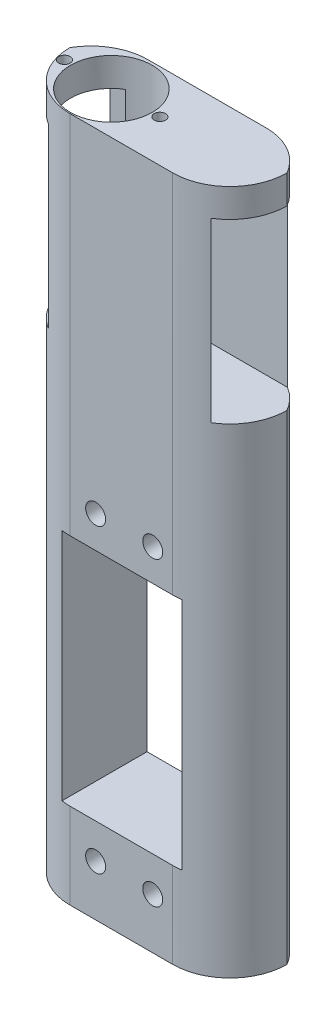
SolidWorks part; units mm, degrees
ref_plane "Front Plane" through (0, 0, 0) normal (0, 0, 1) x (1, 0, 0)
ref_plane "Top Plane" through (0, 0, 0) normal (0, 1, 0) x (1, 0, 0)
ref_plane "Right Plane" through (0, 0, 0) normal (1, 0, 0) x (0, 0, -1)
sketch "Sketch1" plane through (0, 0, 0) normal (0, 0, 1) x (1, 0, 0)
  line L1 (-20.7438, 48.8926) -> (17.2562, 48.8926)
  line L2 (-20.7438, 48.8926) -> (-20.7438, -71.1074)
  line L3 (-20.7438, -71.1074) -> (17.2562, -71.1074)
  line L4 (17.2562, 48.8926) -> (17.2562, -71.1074)
  dimension "D1" = 120
  dimension "D2" = 38
extrude "Boss-Extrude1" add sketch "Sketch1" along normal blind 15
sketch "Sketch2" plane through (0, 0, 15) normal (0, 0, 1) x (1, 0, 0)
  line L0 (-20.7438, -71.1074) -> (17.2562, -71.1074) construction
  line L1 (-12.2438, -15.1074) -> (8.7562, -15.1074)
  line L2 (-12.2438, -15.1074) -> (-12.2438, -56.1074)
  line L3 (-12.2438, -56.1074) -> (8.7562, -56.1074)
  line L4 (8.7562, -15.1074) -> (8.7562, -56.1074)
  line L5 (-20.7438, 48.8926) -> (-20.7438, -71.1074) construction
  dimension "D1" = 41
  dimension "D2" = 21
  dimension "D3" = 15
  dimension "D4" = 8.5
extrude "Cut-Extrude2" cut sketch "Sketch2" against normal blind 15 contours L2 L1 L4 L3
sketch "Sketch3" plane through (0, 0, 15) normal (0, 0, 1) x (1, 0, 0)
  circle A0 centre (-6.2438, -9.5176) radius 1.75
  circle A1 centre (3.7562, -9.5176) radius 1.75
  circle A3 centre (-6.2438, -62.2156) radius 1.75
  circle A4 centre (3.7562, -62.2156) radius 1.75
  dimension "D1" = 3.5
  dimension "D2" = 3.5
  dimension "D4" = 3.5
  dimension "D5" = 3.5
  dimension "D6" = 3.5
  dimension "D11" = 3.5
  dimension "D3" = 10
  dimension "D7" = 5
  dimension "D8" = 5
  dimension "D9" = 6
  dimension "D10" = 6
extrude "Cut-Extrude4" cut sketch "Sketch3" against normal blind 15
sketch "Sketch5"
sketch "Sketch6" plane through (17.2562, 0, 0) normal (1, 0, 0) x (0, 0, -1)
  line L0 (-15, 48.8926) -> (0, 48.8926) construction
  line L1 (-13.5313, 43.8926) -> (-1.4687, 43.8926)
  line L2 (-13.5313, 43.8926) -> (-13.5313, 12.8926)
  line L3 (-13.5313, 12.8926) -> (-1.4687, 12.8926)
  line L4 (-1.4687, 43.8926) -> (-1.4687, 12.8926)
  dimension "D1" = 5
  dimension "D2" = 31
  dimension "D3" = 12.0626
extrude "Cut-Extrude8" cut sketch "Sketch6" against normal blind 38
sketch "Sketch8" plane through (0, 48.8926, 0) normal (0, 1, 0) x (1, 0, 0)
  circle A0 centre (-10.8647, -7.6288) radius 7.1555
  circle A1 centre (-19.3647, -7.3404) radius 1
  circle A2 centre (-2.3647, -7.6288) radius 1
  point P6 (-19.8062, -7.5522)
  point P7 (0, 0)
  point P8 (-19.6001, -7.342)
  point P9 (0, 0)
  point P10 (10.3982, -8.7963)
  point P11 (0, 0)
  point P12 (-10.8647, -7.6288)
  point P13 (-10.8235, -7.548)
  dimension "D1" = 2
  dimension "D3" = 2
  dimension "D2" = 8.5049
  dimension "D4" = 8.5
  dimension "D5" = 8.5
extrude "Cut-Extrude10" cut sketch "Sketch8" against normal blind 10
fillet "Fillet2" radius 10 2 edges at (-20.7438, -11.1074, 15) (17.2562, -11.1074, 15)
fillet "Fillet3" radius 10 2 edges at (-20.7438, -11.1074, 0) (17.2562, -11.1074, 0)
